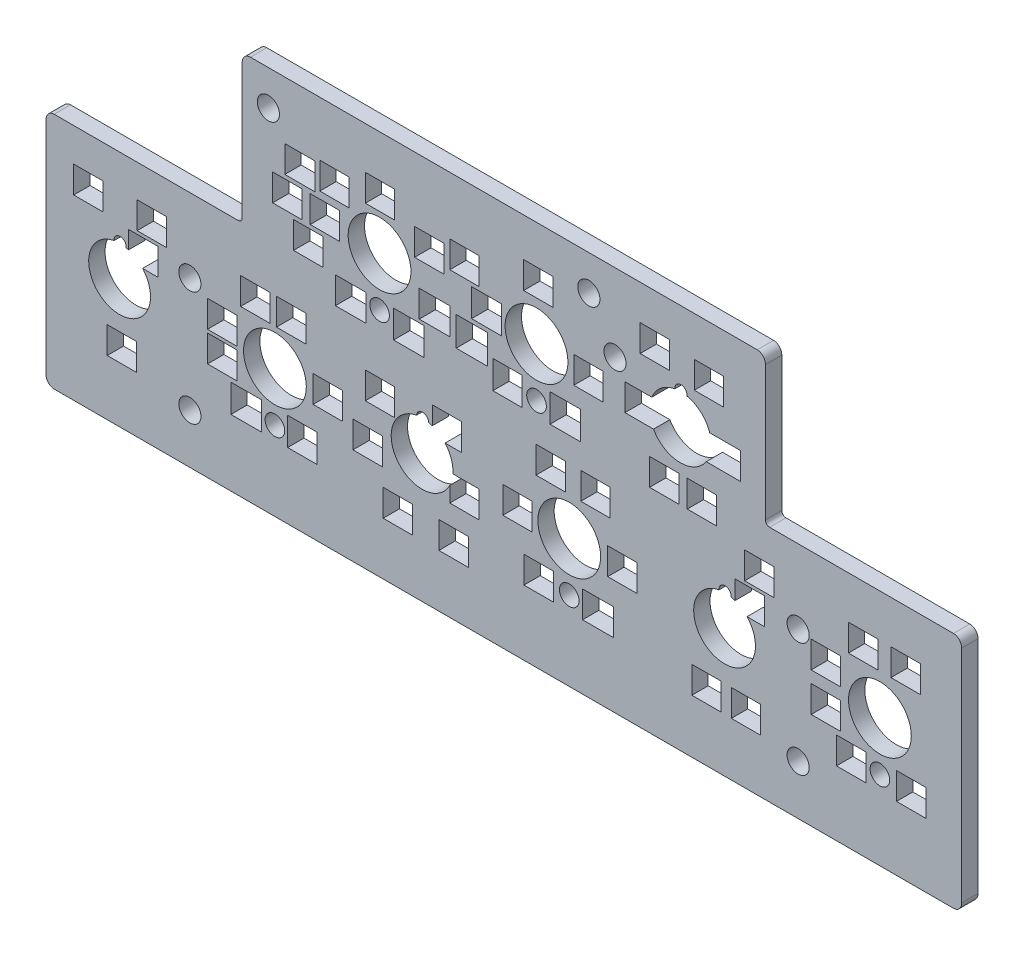
SolidWorks part; units mm, degrees
material "Acrylic (Medium-high impact)"
ref_plane "Front Plane" through (0, 0, 0) normal (0, 0, 1) x (1, 0, 0)
ref_plane "Top Plane" through (0, 0, 0) normal (0, 1, 0) x (1, 0, 0)
ref_plane "Right Plane" through (0, 0, 0) normal (1, 0, 0) x (0, 0, -1)
sketch "Sketch1" plane through (0, 0, 0) normal (0, 0, 1) x (1, 0, 0)
  line L8 (-51.5937, 5.4323) -> (-87.3125, 5.4323)
  line L9 (-88.9, 3.7429) -> (-88.9, -39.0998)
  line L10 (-87.3125, -40.7892) -> (87.3125, -40.7892)
  line L11 (88.9, -39.0998) -> (88.9, 3.7429)
  line L12 (87.3125, 5.4323) -> (51.5938, 5.4323)
  line L13 (50.8, 6.277) -> (50.8, 32.3948)
  line L14 (49.2125, 34.0842) -> (-49.2125, 34.0842)
  line L15 (-50.8, 32.3948) -> (-50.8, 6.277)
  line L16 (-51.5937, 5.4323) -> (-87.3125, 5.4323)
  line L17 (-88.9, 3.7429) -> (-88.9, -39.0998)
  line L18 (-87.3125, -40.7892) -> (87.3125, -40.7892)
  line L19 (88.9, -39.0998) -> (88.9, 3.7429)
  line L20 (87.3125, 5.4323) -> (51.5938, 5.4323)
  line L21 (50.8, 6.277) -> (50.8, 32.3948)
  line L22 (49.2125, 34.0842) -> (-49.2125, 34.0842)
  line L23 (-50.8, 32.3948) -> (-50.8, 6.277)
  ellipse E8 centre (87.3125, 3.7429) end of major axis (87.3125, 2.0535) minor radius 1.5875 (88.9, 3.7429) -> (87.3125, 5.4323) ccw
  ellipse E9 centre (87.3125, 3.7429) end of major axis (87.3125, 2.0535) minor radius 1.5875 (88.9, 3.7429) -> (87.3125, 5.4323) ccw
  ellipse E10 centre (49.2125, 32.3948) end of major axis (49.2125, 34.0842) minor radius 1.5875 (50.8, 32.3948) -> (49.2125, 34.0842) ccw
  ellipse E11 centre (49.2125, 32.3948) end of major axis (49.2125, 34.0842) minor radius 1.5875 (50.8, 32.3948) -> (49.2125, 34.0842) ccw
  ellipse E12 centre (51.5938, 6.277) end of major axis (51.5938, 5.4323) minor radius 0.7938 (50.8, 6.277) -> (51.5938, 5.4323) ccw
  ellipse E13 centre (51.5938, 6.277) end of major axis (51.5938, 5.4323) minor radius 0.7938 (50.8, 6.277) -> (51.5938, 5.4323) ccw
  ellipse E14 centre (-51.5937, 6.277) end of major axis (-51.5937, 5.4323) minor radius 0.7938 (-51.5937, 5.4323) -> (-50.8, 6.277) ccw
  ellipse E15 centre (-51.5937, 6.277) end of major axis (-51.5937, 5.4323) minor radius 0.7938 (-51.5937, 5.4323) -> (-50.8, 6.277) ccw
  ellipse E28 centre (-49.2125, 32.3948) end of major axis (-49.2125, 34.0842) minor radius 1.5875 (-49.2125, 34.0842) -> (-50.8, 32.3948) ccw
  ellipse E29 centre (-49.2125, 32.3948) end of major axis (-49.2125, 34.0842) minor radius 1.5875 (-49.2125, 34.0842) -> (-50.8, 32.3948) ccw
  ellipse E30 centre (-87.3125, 3.7429) end of major axis (-87.3125, 2.0535) minor radius 1.5875 (-87.3125, 5.4323) -> (-88.9, 3.7429) ccw
  ellipse E31 centre (-87.3125, 3.7429) end of major axis (-87.3125, 2.0535) minor radius 1.5875 (-87.3125, 5.4323) -> (-88.9, 3.7429) ccw
  ellipse E32 centre (-87.3125, -39.0998) end of major axis (-87.3125, -37.4104) minor radius 1.5875 (-88.9, -39.0998) -> (-87.3125, -40.7892) ccw
  ellipse E33 centre (-87.3125, -39.0998) end of major axis (-87.3125, -37.4104) minor radius 1.5875 (-88.9, -39.0998) -> (-87.3125, -40.7892) ccw
  ellipse E34 centre (87.3125, -39.0998) end of major axis (87.3125, -37.4104) minor radius 1.5875 (87.3125, -40.7892) -> (88.9, -39.0998) ccw
  ellipse E35 centre (87.3125, -39.0998) end of major axis (87.3125, -37.4104) minor radius 1.5875 (87.3125, -40.7892) -> (88.9, -39.0998) ccw
  dimension "D1" = 0
extrude "Boss-Extrude1" add sketch "Sketch1" along normal blind 3.175
sketch "Sketch2" plane through (0, 0, 3.175) normal (0, 0, 1) x (1, 0, 0)
  arc A4 (-72.0725, -25.0899) -> (-77.1525, -25.0899) centre (-74.6125, -15.9098) ccw construction
  arc A5 (-14.2875, -23.6221) -> (-17.4625, -23.6221) centre (-15.875, -15.9098) ccw construction
  arc A6 (45.4025, -25.0899) -> (40.3225, -25.0899) centre (42.8625, -15.9098) ccw construction
  arc A7 (35.8775, 5.9054) -> (32.7025, 5.9054) centre (34.29, 13.6177) ccw construction
  circle A8 centre (42.8625, -15.9098) radius 3.7703
  circle A9 centre (-15.875, -15.9098) radius 3.7703
  circle A10 centre (-74.6125, -15.9098) radius 3.7703
  circle A11 centre (34.29, 13.6177) radius 3.7703
  dimension "D1" = 7.5406
extrude "Cut-Extrude1" cut sketch "Sketch2" against normal through all
sketch "Sketch4" plane through (0, 0, 3.175) normal (0, 0, 1) x (1, 0, 0)
  circle A0 centre (73.025, -15.9098) radius 6.096
  circle A1 centre (12.7, -15.9098) radius 6.096
  circle A2 centre (-44.45, -15.9098) radius 6.096
  circle A3 centre (-24.13, 13.6177) radius 6.096
  circle A4 centre (6.35, 13.6177) radius 6.096
  circle A5 centre (73.025, -25.4348) radius 1.905
  circle A6 centre (12.7, -25.4348) radius 1.905
  circle A7 centre (-44.45, -25.4348) radius 1.905
  circle A8 centre (6.35, 4.0927) radius 1.905
  circle A9 centre (-24.13, 4.0927) radius 1.905
  dimension "D1" = 12.192
  dimension "D2" = 3.81
  dimension "D3" = 9.525
  dimension "D4" = 9.525
extrude "Cut-Extrude2" cut sketch "Sketch4" against normal through all
hole_wizard "#6 Clearance Hole1" positions "Sketch6" profile "Sketch5" hole size "#6" standard "ANSI Inch" end condition through all
sketch "Sketch6" plane through (0, 0, 3.175) normal (0, 0, 1) x (1, 0, 0)
  point P0 (-45.72, 27.2702)
  point P3 (16.51, 27.2702)
  point P6 (21.59, 19.0152)
  point P9 (57.15, -8.9248)
  point P12 (57.15, -31.1498)
  point P15 (-60.96, -31.1498)
  point P18 (-60.96, -8.9248)
sketch "Sketch5" plane through (-45.72, 27.2702, 3.175) normal (1, 0, 0) x (0, -1, 0)
  line L0 (0, 0) -> (0, 3.175)
  line L1 (0, 3.175) -> (2.1526, 3.175)
  line L2 (2.1526, 3.175) -> (2.1526, 0)
  line L5 (2.1526, 0) -> (0, 0)
  line L11 (0, -6.35) -> (0, 107.95) construction
  dimension "Thru Hole Dia." = 4.3053
  dimension "Thru Hole Depth" = 3.175
fillet "Fillet1" [suppressed] radius 1.5875
sketch "Sketch7" plane through (0, 0, 3.175) normal (0, 0, 1) x (1, 0, 0)
  circle A0 centre (42.967, -9.9107) radius 1.1906
  circle A1 centre (-15.774, -10.1107) radius 1.1906
  circle A2 centre (-74.508, -9.9107) radius 1.1906
  circle A3 centre (34.3945, 19.6168) radius 1.1906
  dimension "D1" = 2.3813
extrude "Cut-Extrude3" cut sketch "Sketch7" against normal through all
sketch "Sketch8" plane through (0, 0, 3.175) normal (0, 0, 1) x (1, 0, 0)
  line L0 (-51.5937, 5.4323) -> (-87.3125, 5.4323)
  line L1 (-50.8, 32.3948) -> (-50.8, 6.277)
  line L2 (49.2125, 34.0842) -> (-49.2125, 34.0842)
  line L3 (50.8, 6.277) -> (50.8, 32.3948)
  line L4 (87.3125, 5.4323) -> (51.5937, 5.4323)
  line L5 (88.9, -39.0998) -> (88.9, 3.7429)
  line L6 (-87.3125, -40.7892) -> (87.3125, -40.7892)
  line L7 (-88.9, 3.7429) -> (-88.9, -39.0998)
  line L8 (-57.5339, -21.6677) -> (-51.8339, -21.6677)
  line L9 (-51.8339, -21.6677) -> (-51.8339, -16.4677)
  line L10 (-51.8339, -16.4677) -> (-57.5339, -16.4677)
  line L11 (-57.5339, -16.4677) -> (-57.5339, -21.6677)
  line L12 (-16.4246, 6.4236) -> (-10.4907, 6.4236)
  line L13 (-10.4907, 6.4236) -> (-10.4907, 11.6236)
  line L14 (-10.4907, 11.6236) -> (-16.4246, 11.6236)
  line L15 (-16.4246, 11.6236) -> (-16.4246, 6.4236)
  line L16 (3.8516, 21.3751) -> (9.5516, 21.3751)
  line L17 (9.5516, 21.3751) -> (9.5516, 26.5751)
  line L18 (9.5516, 26.5751) -> (3.8516, 26.5751)
  line L19 (3.8516, 26.5751) -> (3.8516, 21.3751)
  line L20 (-2.1329, 1.5322) -> (3.5671, 1.5322)
  line L21 (3.5671, 1.5322) -> (3.5671, 6.9801)
  line L22 (3.5671, 6.9801) -> (-2.1329, 6.9801)
  line L23 (-2.1329, 6.9801) -> (-2.1329, 1.5322)
  line L24 (13.5869, 10.3093) -> (19.2869, 10.3093)
  line L25 (19.2869, 10.3093) -> (19.2869, 15.5093)
  line L26 (19.2869, 15.5093) -> (13.5869, 15.5093)
  line L27 (13.5869, 15.5093) -> (13.5869, 10.3093)
  line L28 (-23.4257, -30.562) -> (-17.7257, -30.562)
  line L29 (-17.7257, -30.562) -> (-17.7257, -25.362)
  line L30 (-17.7257, -25.362) -> (-23.4257, -25.362)
  line L31 (-23.4257, -25.362) -> (-23.4257, -30.562)
  line L32 (-17.3237, 16.3707) -> (-11.6237, 16.3707)
  line L33 (-11.6237, 16.3707) -> (-11.6237, 21.5707)
  line L34 (-11.6237, 21.5707) -> (-17.3237, 21.5707)
  line L35 (-17.3237, 21.5707) -> (-17.3237, 16.3707)
  line L36 (-26.8936, 20.6839) -> (-21.1936, 20.6839)
  line L37 (-21.1936, 20.6839) -> (-21.1936, 25.8839)
  line L38 (-21.1936, 25.8839) -> (-26.8936, 25.8839)
  line L39 (-26.8936, 25.8839) -> (-26.8936, 20.6839)
  line L40 (-6.2605, 11.5858) -> (-0.4348, 11.5858)
  line L41 (-0.4348, 11.5858) -> (-0.4348, 16.9765)
  line L42 (-0.4348, 16.9765) -> (-6.2605, 16.9765)
  line L43 (-6.2605, 16.9765) -> (-6.2605, 11.5858)
  line L44 (3.902, -28.1405) -> (9.602, -28.1405)
  line L45 (9.602, -28.1405) -> (9.602, -22.9405)
  line L46 (9.602, -22.9405) -> (3.902, -22.9405)
  line L47 (3.902, -22.9405) -> (3.902, -28.1405)
  line L48 (20.173, -18.5822) -> (25.873, -18.5822)
  line L49 (25.873, -18.5822) -> (25.873, -13.3822)
  line L50 (25.873, -13.3822) -> (20.173, -13.3822)
  line L51 (20.173, -13.3822) -> (20.173, -18.5822)
  line L52 (-0.184, -18.4363) -> (5.516, -18.4363)
  line L53 (5.516, -18.4363) -> (5.516, -13.2363)
  line L54 (5.516, -13.2363) -> (-0.184, -13.2363)
  line L55 (-0.184, -13.2363) -> (-0.184, -18.4363)
  line L56 (6.2437, -8.4752) -> (11.9437, -8.4752)
  line L57 (11.9437, -8.4752) -> (11.9437, -3.2752)
  line L58 (11.9437, -3.2752) -> (6.2437, -3.2752)
  line L59 (6.2437, -3.2752) -> (6.2437, -8.4752)
  line L60 (23.5207, 10.6712) -> (29.0633, 10.6712)
  line L62 (28.7293, 15.8712) -> (23.5207, 15.8712)
  line L63 (23.5207, 15.8712) -> (23.5207, 10.6712)
  line L64 (40.2759, 10.3093) -> (45.9759, 10.3093)
  line L65 (45.9759, 10.3093) -> (45.9759, 15.5093)
  line L66 (45.9759, 15.5093) -> (40.2759, 15.5093)
  line L68 (36.9852, 21.1664) -> (42.6852, 21.1664)
  line L69 (42.6852, 21.1664) -> (42.6852, 26.3664)
  line L70 (42.6852, 26.3664) -> (36.9852, 26.3664)
  line L71 (36.9852, 26.3664) -> (36.9852, 21.1664)
  line L72 (26.4638, 22.0824) -> (32.1638, 22.0824)
  line L73 (32.1638, 22.0824) -> (32.1638, 27.2824)
  line L74 (32.1638, 27.2824) -> (26.4638, 27.2824)
  line L75 (26.4638, 27.2824) -> (26.4638, 22.0824)
  line L76 (-29.302, -22.0056) -> (-23.602, -22.0056)
  line L77 (-23.602, -22.0056) -> (-23.602, -16.8056)
  line L78 (-23.602, -16.8056) -> (-29.302, -16.8056)
  line L79 (-29.302, -16.8056) -> (-29.302, -22.0056)
  line L80 (-26.8936, -12.5459) -> (-21.1936, -12.5459)
  line L81 (-21.1936, -12.5459) -> (-21.1936, -7.3459)
  line L82 (-21.1936, -7.3459) -> (-26.8936, -7.3459)
  line L83 (-26.8936, -7.3459) -> (-26.8936, -12.5459)
  line L84 (-10.4862, -21.537) -> (-4.7862, -21.537)
  line L85 (-4.7862, -21.537) -> (-4.7862, -16.337)
  line L86 (-4.7862, -16.337) -> (-9.8902, -16.337)
  line L87 (-10.4862, -18.5481) -> (-10.4862, -21.537)
  line L88 (-11.4038, -11.9088) -> (-8.1877, -11.9088)
  line L89 (-8.1877, -11.9088) -> (-8.1877, -6.7088)
  line L90 (-8.1877, -6.7088) -> (-13.8877, -6.7088)
  line L91 (-13.8877, -6.7088) -> (-13.8877, -10.2485)
  line L92 (-51.1023, -8.787) -> (-45.4023, -8.787)
  line L93 (-45.4023, -8.787) -> (-45.4023, -3.587)
  line L94 (-45.4023, -3.587) -> (-51.1023, -3.587)
  line L95 (-51.1023, -3.587) -> (-51.1023, -8.787)
  line L96 (-37.0315, -18.226) -> (-31.3315, -18.226)
  line L97 (-31.3315, -18.226) -> (-31.3315, -13.026)
  line L98 (-31.3315, -13.026) -> (-37.0315, -13.026)
  line L99 (-37.0315, -13.026) -> (-37.0315, -18.226)
  line L100 (-70.1435, -11.9063) -> (-67.1781, -11.9063)
  line L101 (-67.1781, -11.9063) -> (-67.1781, -6.7063)
  line L102 (-67.1781, -6.7063) -> (-72.8781, -6.7063)
  line L103 (-72.8781, -6.7063) -> (-72.8781, -10.1659)
  line L104 (-71.2049, -6.0898) -> (-65.5049, -6.0898)
  line L105 (-65.5049, -6.0898) -> (-65.5049, -0.8898)
  line L106 (-65.5049, -0.8898) -> (-71.2049, -0.8898)
  line L107 (-71.2049, -0.8898) -> (-71.2049, -6.0898)
  line L108 (64.5921, -28.1957) -> (70.2921, -28.1957)
  line L109 (70.2921, -28.1957) -> (70.2921, -22.9957)
  line L110 (70.2921, -22.9957) -> (64.5921, -22.9957)
  line L111 (64.5921, -22.9957) -> (64.5921, -28.1957)
  line L112 (-37.5953, 11.7476) -> (-31.8953, 11.7476)
  line L113 (-31.8953, 11.7476) -> (-31.8953, 16.9476)
  line L114 (-31.8953, 16.9476) -> (-37.5953, 16.9476)
  line L115 (-37.5953, 16.9476) -> (-37.5953, 11.7476)
  line L116 (-9.2553, 5.1211) -> (-3.1441, 5.1211)
  line L117 (-3.1441, 5.1211) -> (-3.1441, 10.7909)
  line L118 (-3.1441, 10.7909) -> (-9.2553, 10.7909)
  line L119 (-9.2553, 10.7909) -> (-9.2553, 5.1211)
  line L120 (-21.4064, 0.4179) -> (-15.468, 0.4179)
  line L121 (-15.468, 0.4179) -> (-15.468, 5.7877)
  line L122 (-15.468, 5.7877) -> (-21.4064, 5.7877)
  line L123 (-21.4064, 5.7877) -> (-21.4064, 0.4179)
  line L124 (59.6809, -22.0056) -> (65.3809, -22.0056)
  line L125 (65.3809, -22.0056) -> (65.3809, -16.8056)
  line L126 (65.3809, -16.8056) -> (59.6809, -16.8056)
  line L127 (59.6809, -16.8056) -> (59.6809, -22.0056)
  line L128 (-35.7321, 18.305) -> (-30.0321, 18.305)
  line L129 (-30.0321, 18.305) -> (-30.0321, 23.505)
  line L130 (-30.0321, 23.505) -> (-35.7321, 23.505)
  line L131 (-35.7321, 23.505) -> (-35.7321, 18.305)
  line L132 (-32.7001, 0.5426) -> (-26.7664, 0.5426)
  line L133 (-26.7664, 0.5426) -> (-26.7664, 5.7426)
  line L134 (-26.7664, 5.7426) -> (-32.7001, 5.7426)
  line L135 (-32.7001, 5.7426) -> (-32.7001, 0.5426)
  line L136 (-57.5339, -15.8363) -> (-51.8339, -15.8363)
  line L137 (-51.8339, -15.8363) -> (-51.8339, -10.6363)
  line L138 (-51.8339, -10.6363) -> (-57.5339, -10.6363)
  line L139 (-57.5339, -10.6363) -> (-57.5339, -15.8363)
  line L140 (-77.0213, -29.9931) -> (-71.3213, -29.9931)
  line L141 (-71.3213, -29.9931) -> (-71.3213, -24.7931)
  line L142 (-71.3213, -24.7931) -> (-77.0213, -24.7931)
  line L143 (-77.0213, -24.7931) -> (-77.0213, -29.9931)
  line L144 (-41.9767, -27.9461) -> (-36.2767, -27.9461)
  line L145 (-36.2767, -27.9461) -> (-36.2767, -22.5204)
  line L146 (-36.2767, -22.5204) -> (-41.9767, -22.5204)
  line L147 (-41.9767, -22.5204) -> (-41.9767, -27.9461)
  line L148 (76.2478, -28.3416) -> (81.9478, -28.3416)
  line L149 (81.9478, -28.3416) -> (81.9478, -23.1416)
  line L150 (81.9478, -23.1416) -> (76.2478, -23.1416)
  line L151 (76.2478, -23.1416) -> (76.2478, -28.3416)
  line L152 (-40.8349, 5.7772) -> (-35.1349, 5.7772)
  line L153 (-35.1349, 5.7772) -> (-35.1349, 10.9772)
  line L154 (-35.1349, 10.9772) -> (-40.8349, 10.9772)
  line L155 (-40.8349, 10.9772) -> (-40.8349, 5.7772)
  line L156 (-83.5151, -6.2491) -> (-77.8151, -6.2491)
  line L157 (-77.8151, -6.2491) -> (-77.8151, -1.0491)
  line L158 (-77.8151, -1.0491) -> (-83.5151, -1.0491)
  line L159 (-83.5151, -1.0491) -> (-83.5151, -6.2491)
  line L160 (-44.1583, -8.787) -> (-38.4583, -8.787)
  line L161 (-38.4583, -8.787) -> (-38.4583, -3.587)
  line L162 (-38.4583, -3.587) -> (-44.1583, -3.587)
  line L163 (-44.1583, -3.587) -> (-44.1583, -8.787)
  line L164 (-52.9981, -27.8943) -> (-47.0898, -27.8943)
  line L165 (-47.0898, -27.8943) -> (-47.0898, -22.463)
  line L166 (-47.0898, -22.463) -> (-52.9981, -22.463)
  line L167 (-52.9981, -22.463) -> (-52.9981, -27.8943)
  line L168 (15.2844, -28.2864) -> (21.2964, -28.2864)
  line L169 (21.2964, -28.2864) -> (21.2964, -23.0864)
  line L170 (21.2964, -23.0864) -> (15.2844, -23.0864)
  line L171 (15.2844, -23.0864) -> (15.2844, -28.2864)
  line L172 (-44.8849, 11.7476) -> (-39.1849, 11.7476)
  line L173 (-39.1849, 11.7476) -> (-39.1849, 16.9476)
  line L174 (-39.1849, 16.9476) -> (-44.8849, 16.9476)
  line L175 (-44.8849, 16.9476) -> (-44.8849, 11.7476)
  line L176 (75.1693, -8.0633) -> (80.8693, -8.0633)
  line L177 (80.8693, -8.0633) -> (80.8693, -2.8633)
  line L178 (80.8693, -2.8633) -> (75.1693, -2.8633)
  line L179 (75.1693, -2.8633) -> (75.1693, -8.0633)
  line L180 (44.1756, -30.4188) -> (49.8756, -30.4188)
  line L181 (49.8756, -30.4188) -> (49.8756, -25.2188)
  line L182 (49.8756, -25.2188) -> (44.1756, -25.2188)
  line L183 (44.1756, -25.2188) -> (44.1756, -30.4188)
  line L184 (47.2241, -11.7896) -> (50.5854, -11.7896)
  line L185 (50.5854, -11.7896) -> (50.5854, -6.5896)
  line L186 (50.5854, -6.5896) -> (44.8854, -6.5896)
  line L187 (44.8854, -6.5896) -> (44.8854, -10.2611)
  line L188 (28.302, 0.5017) -> (34.002, 0.5017)
  line L189 (34.002, 0.5017) -> (34.002, 5.7017)
  line L190 (34.002, 5.7017) -> (28.302, 5.7017)
  line L191 (28.302, 5.7017) -> (28.302, 0.5017)
  line L192 (46.7612, -5.9836) -> (52.4612, -5.9836)
  line L193 (52.4612, -5.9836) -> (52.4612, -0.7836)
  line L194 (52.4612, -0.7836) -> (46.7612, -0.7836)
  line L195 (46.7612, -0.7836) -> (46.7612, -5.9836)
  line L196 (36.5158, -30.3563) -> (42.2158, -30.3563)
  line L197 (42.2158, -30.3563) -> (42.2158, -25.1563)
  line L198 (42.2158, -25.1563) -> (36.5158, -25.1563)
  line L199 (36.5158, -25.1563) -> (36.5158, -30.3563)
  line L200 (8.9659, 1.4426) -> (14.8998, 1.4426)
  line L201 (14.8998, 1.4426) -> (14.8998, 6.9217)
  line L202 (14.8998, 6.9217) -> (8.9659, 6.9217)
  line L203 (8.9659, 6.9217) -> (8.9659, 1.4426)
  line L204 (59.6809, -14.5136) -> (65.3809, -14.5136)
  line L205 (65.3809, -14.5136) -> (65.3809, -9.3136)
  line L206 (65.3809, -9.3136) -> (59.6809, -9.3136)
  line L207 (59.6809, -9.3136) -> (59.6809, -14.5136)
  line L208 (-10.4862, 17.696) -> (-4.7862, 17.696)
  line L209 (-4.7862, 17.696) -> (-4.7862, 22.896)
  line L210 (-4.7862, 22.896) -> (-10.4862, 22.896)
  line L211 (-10.4862, 22.896) -> (-10.4862, 17.696)
  line L212 (35.615, 0.5017) -> (41.315, 0.5017)
  line L213 (41.315, 0.5017) -> (41.315, 5.7017)
  line L214 (41.315, 5.7017) -> (35.615, 5.7017)
  line L215 (35.615, 5.7017) -> (35.615, 0.5017)
  line L216 (-12.6071, -30.562) -> (-6.9071, -30.562)
  line L217 (-6.9071, -30.562) -> (-6.9071, -25.362)
  line L218 (-6.9071, -25.362) -> (-12.6071, -25.362)
  line L219 (-12.6071, -25.362) -> (-12.6071, -30.562)
  line L220 (-42.534, 17.696) -> (-36.6383, 17.696)
  line L221 (-36.6383, 17.696) -> (-36.6383, 22.896)
  line L222 (-36.6383, 22.896) -> (-42.534, 22.896)
  line L223 (-42.534, 22.896) -> (-42.534, 17.696)
  line L224 (66.9091, -8.0633) -> (72.6091, -8.0633)
  line L225 (72.6091, -8.0633) -> (72.6091, -2.8633)
  line L226 (72.6091, -2.8633) -> (66.9091, -2.8633)
  line L227 (66.9091, -2.8633) -> (66.9091, -8.0633)
  line L228 (14.9533, -8.5151) -> (20.6533, -8.5151)
  line L229 (20.6533, -8.5151) -> (20.6533, -3.3151)
  line L230 (20.6533, -3.3151) -> (14.9533, -3.3151)
  line L231 (14.9533, -3.3151) -> (14.9533, -8.5151)
  line L233 (40.2759, 15.5093) -> (39.984, 15.5093)
  line L234 (40.2759, 10.3093) -> (39.2955, 10.3093)
  circle A0 centre (42.8625, -15.9098) radius 3.7703
  circle A1 centre (-15.875, -15.9098) radius 3.7703
  circle A2 centre (-74.6125, -15.9098) radius 3.7703
  circle A3 centre (34.29, 13.6177) radius 3.7703
  circle A4 centre (73.025, -15.9098) radius 6.096
  circle A5 centre (12.7, -15.9098) radius 6.096
  circle A6 centre (-44.45, -15.9098) radius 6.096
  circle A7 centre (-24.13, 13.6177) radius 6.096
  circle A8 centre (6.35, 13.6177) radius 6.096
  circle A9 centre (73.025, -25.4348) radius 1.905
  circle A10 centre (12.7, -25.4348) radius 1.905
  circle A11 centre (-44.45, -25.4348) radius 1.905
  circle A12 centre (6.35, 4.0927) radius 1.905
  circle A13 centre (-24.13, 4.0927) radius 1.905
  circle A14 centre (-60.96, -8.9248) radius 2.1527
  circle A15 centre (-60.96, -31.1498) radius 2.1527
  circle A16 centre (57.15, -31.1498) radius 2.1526
  circle A17 centre (57.15, -8.9248) radius 2.1526
  circle A18 centre (21.59, 19.0152) radius 2.1527
  circle A19 centre (16.51, 27.2702) radius 2.1526
  circle A20 centre (-45.72, 27.2702) radius 2.1527
  circle A21 centre (34.3945, 19.6168) radius 1.1906
  circle A22 centre (-74.508, -9.9107) radius 1.1906
  circle A23 centre (-15.774, -10.1107) radius 1.1906
  circle A24 centre (42.967, -9.9107) radius 1.1906
  arc A25 (-51.5937, 5.4323) -> (-50.8, 6.277) centre (-51.619, 6.2513) ccw
  arc A26 (-49.2125, 34.0842) -> (-50.8, 32.3948) centre (-49.1599, 32.4443) ccw
  arc A27 (50.8, 32.3948) -> (49.2125, 34.0842) centre (49.1599, 32.4443) ccw
  arc A28 (50.8, 6.277) -> (51.5937, 5.4323) centre (51.6211, 6.2533) ccw
  arc A29 (88.9, 3.7429) -> (87.3125, 5.4323) centre (87.2599, 3.7923) ccw
  arc A30 (87.3125, -40.7892) -> (88.9, -39.0998) centre (87.2599, -39.1492) ccw
  arc A31 (-88.9, -39.0998) -> (-87.3125, -40.7892) centre (-87.2621, -39.1512) ccw
  arc A32 (-87.3125, 5.4323) -> (-88.9, 3.7429) centre (-87.2599, 3.7923) ccw
  arc A33 (44.8854, -10.2611) -> (47.2241, -11.7896) centre (42.8625, -15.9098) ccw
  arc A34 (-9.8902, -16.337) -> (-11.4038, -11.9088) centre (-15.875, -15.9098) ccw
  arc A35 (-72.8781, -10.1659) -> (-70.1435, -11.9063) centre (-74.6125, -15.9098) ccw
  arc A36 (29.0633, 10.6712) -> (39.2955, 10.3093) centre (34.29, 13.6177) ccw
  arc A37 (-13.8877, -10.2485) -> (-10.4862, -18.5481) centre (-15.875, -15.9098) ccw
  arc A38 (39.984, 15.5093) -> (28.7293, 15.8712) centre (34.29, 13.6177) ccw
  dimension "D1" = 12
  dimension "D2" = 12
  dimension "D3" = 12
  dimension "D4" = 12
extrude "Backlighting LED holes" cut sketch "Sketch8" against normal up to next (3.175 mm away) contours L150 L151 L148 L149 | L110 L111 L108 L109 | L126 L127 L124 L125 | L206 L207 L204 L205 | L226 L227 L224 L225 | L178 L179 L176 L177 | L182 L183 L180 L181 | L198 L199 L196 L197 | L186 L187 L184 L185 | L194 L195 L192 L193 | L170 L171 L168 L169 | L50 L51 L48 L49 | L230 L231 L228 L229 | L58 L59 L56 L57 | L54 L55 L52 L53 | L46 L47 L44 L45 | L86 L87 L84 L85 | L218 L219 L216 L217 | L30 L31 L28 L29 | L78 L79 L76 L77 | L82 L83 L80 L81 | L90 L91 L88 L89 | L98 L99 L96 L97 | L146 L147 L144 L145 | L162 L163 L160 L161 | L94 L95 L92 L93 | L166 L167 L164 L165 | L10 L11 L8 L9 | L138 L139 L136 L137 | L102 L103 L100 L101 | L106 L107 L104 L105 | L158 L159 L156 L157 | L142 L143 L140 L141 | L154 L155 L152 L153 | L114 L115 L112 L113 | L130 L131 L128 L129 | L222 L223 L220 L221 | L174 L175 L172 L173 | L134 L135 L132 L133 | L122 L123 L120 L121 | L14 L15 L12 L13 | L34 L35 L32 L33 | L38 L39 L36 L37 | L210 L211 L208 L209 | L42 L43 L40 L41 | L118 L119 L116 L117 | L22 L23 L20 L21 | L202 L203 L200 L201 | L26 L27 L24 L25 | L18 L19 L16 L17 | L62 L63 L60 | L190 L191 L188 L189 | L214 L215 L212 L213 | L66 L64 L65 | L70 L71 L68 L69 | L74 L75 L72 L73 region at (-54.6839, -19.0677, 3.175) region at (-13.4576, 9.0236, 3.175) region at (6.7016, 23.9751, 3.175) region at (0.7171, 4.2562, 3.175) region at (16.4369, 12.9093, 3.175) region at (-20.5757, -27.962, 3.175) region at (-14.4737, 18.9707, 3.175) region at (-24.0436, 23.2839, 3.175) region at (-3.3476, 14.2812, 3.175) region at (6.752, -25.5405, 3.175) region at (23.023, -15.9822, 3.175) region at (2.666, -15.8363, 3.175) region at (9.0937, -5.8752, 3.175) region at (23.7748, 13.2712, 3.175) region at (39.8352, 23.7664, 3.175) region at (29.3138, 24.6824, 3.175) region at (-26.452, -19.4056, 3.175) region at (-24.0436, -9.9459, 3.175) region at (-10.2575, -20.0425, 3.175) region at (-48.2523, -6.187, 3.175) region at (-34.1815, -15.626, 3.175) region at (-76.4881, -21.3951, 3.175) region at (-68.3549, -3.4898, 3.175) region at (67.4421, -25.5957, 3.175) region at (-34.7453, 14.3476, 3.175) region at (-6.1997, 7.956, 3.175) region at (-18.4372, 3.1028, 3.175) region at (62.5309, -19.4056, 3.175) region at (-32.8821, 20.905, 3.175) region at (-29.7333, 3.1426, 3.175) region at (-54.6839, -13.2363, 3.175) region at (-74.1713, -27.3931, 3.175) region at (-39.1267, -25.2332, 3.175) region at (79.0978, -25.7416, 3.175) region at (-37.9849, 8.3772, 3.175) region at (-80.6651, -3.6491, 3.175) region at (-41.3083, -6.187, 3.175) region at (-50.044, -25.1787, 3.175) region at (18.2904, -25.6864, 3.175) region at (-42.0349, 14.3476, 3.175) region at (78.0193, -5.4633, 3.175) region at (47.0256, -27.8188, 3.175) region at (41.0604, -21.4168, 3.175) region at (31.152, 3.1017, 3.175) region at (49.6112, -3.3836, 3.175) region at (39.3658, -27.7563, 3.175) region at (11.9329, 4.1822, 3.175) region at (62.5309, -11.9136, 3.175) region at (-7.6362, 20.296, 3.175) region at (38.465, 3.1017, 3.175) region at (-9.7571, -27.962, 3.175) region at (-39.5862, 20.296, 3.175) region at (69.7591, -5.4633, 3.175) region at (17.8033, -5.9151, 3.175)
equation "\"D4@Sketch4\"=\"D3@Sketch4\""
